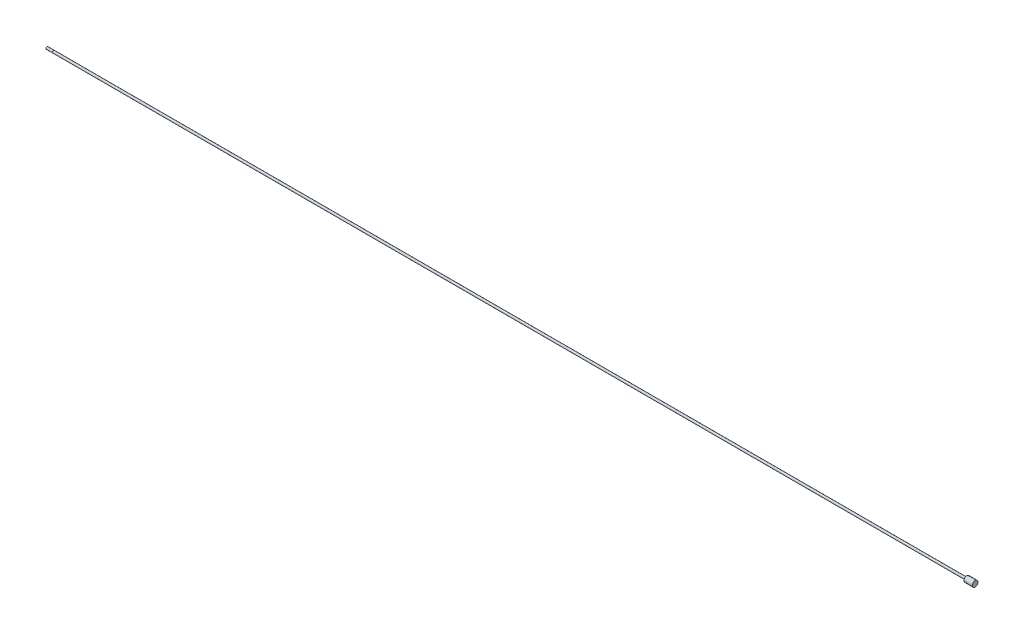
SolidWorks part; units mm, degrees
ref_plane "Front Plane" through (0, 0, 0) normal (0, 0, 1) x (1, 0, 0)
ref_plane "Top Plane" through (0, 0, 0) normal (0, 1, 0) x (1, 0, 0)
ref_plane "Right Plane" through (0, 0, 0) normal (1, 0, 0) x (0, 0, -1)
sketch "Sketch1" plane through (0, 0, 0) normal (0, 0, 1) x (1, 0, 0)
  line L0 (0, 0) -> (0, 1.5875)
  line L1 (0, 1.5875) -> (1291.463, 1.5875)
  line L2 (1291.463, 1.5875) -> (1291.463, 4.0323)
  line L3 (1291.463, 4.0323) -> (1303.3248, 4.0323)
  line L4 (1303.3248, 4.0323) -> (1303.3248, 0)
  line L5 (1303.3248, 0) -> (0, 0)
  line L6 (1303.3248, 0) -> (0, 0) construction
revolve "Revolve1" add sketch "Sketch1" angle 360 about L6 reverse direction yes
cosmetic thread "Cosmetic Thread1" parameters "D1"=9.652, "D2"=2.4181
sketch "Sketch2" plane through (0, 0, 0) normal (0, 0, 1) x (1, 0, 0)
  line L0 (-9.652, 0) -> (-9.652, 1.209)
  line L1 (-9.652, 1.209) -> (-9.2735, 1.5875)
  line L2 (-9.2735, 1.5875) -> (0, 1.5875)
  line L3 (0, 1.5875) -> (0, 0)
  line L4 (0, 0) -> (-9.652, 0)
  line L5 (0, 0) -> (-9.652, 0) construction
revolve "Revolve2" add sketch "Sketch2" angle 360 about L5 reverse direction yes
ref_plane "Plane1" through (0, 0, 0) normal (1, 0, 0) x (0, 0, -1)
ref_plane "Plane2" through (0, 0, 0) normal (1, 0, 0) x (0, 0, -1)
ref_plane "Plane3" through (2594.7878, 0, 0) normal (1, 0, 0) x (0, 0, -1)
ref_plane "Plane4" through (-9.652, 0, 0) normal (1, 0, 0) x (0, 0, -1)
sketch "Sketch3" plane through (0, 0, 0) normal (0, 0, 1) x (1, 0, 0)
  line L0 (-0.254, 1.8415) -> (-0.254, 1.3335)
  line L1 (-0.254, 1.3335) -> (0, 1.3335)
  line L2 (0, 1.3335) -> (0, 1.8415)
  line L3 (0, 1.8415) -> (-0.254, 1.8415)
  line L4 (0, 0) -> (-0.254, 0) construction
revolve "Cut-Revolve1" cut sketch "Sketch3" angle 360 about L4 reverse direction yes
ref_plane "Plane5" through (0, 0, 0) normal (1, 0, 0) x (0, 0, -1)
ref_plane "Plane6" through (0, 0, 0) normal (1, 0, 0) x (0, 0, -1)
ref_plane "Plane7" through (-9.652, 0, 0) normal (1, 0, 0) x (0, 0, -1)
ref_plane "dia1 XY" through (0, 0, 0) normal (1, 0, 0) x (0, 0, -1)
ref_plane "dia1 XZ" through (0, 1.5875, 0) normal (0, -1, 0) x (-1, 0, 0)
ref_plane "dia1 YZ" through (0, 0, 0) normal (0, 0, -1) x (-1, 0, 0)
ref_axis "dia1 X" through (0, 1.5875, 80.9) along (0, 0, -1)
ref_axis "dia1 Y" through (0, -50, 0) along (0, 1, 0)
ref_axis "dia1 Z" through (80.9, 1.5875, 0) along (-1, 0, 0)
sketch3d "dia1"
  point P0 (0, 1.5875, 0)
ref_plane "dia12 XY" through (0, 0, 0) normal (1, 0, 0) x (0, 0, -1)
ref_plane "dia12 XZ" through (0, 0, 0) normal (0, -1, 0) x (-1, 0, 0)
ref_plane "dia12 YZ" through (0, 0, 7.6835) normal (0, 0, -1) x (-1, 0, 0)
ref_axis "dia12 X" through (0, 0, 80.9) along (0, 0, -1)
ref_axis "dia12 Y" through (0, -50, 7.6835) along (0, 1, 0)
ref_axis "dia12 Z" through (80.9, 0, 7.6835) along (-1, 0, 0)
sketch3d "dia12"
  point P0 (0, 0, 7.6835)
ref_plane "dia1r XY" through (0, 0, 0) normal (1, 0, 0) x (0, 0, -1)
ref_plane "dia1r XZ" through (0, 0, 0) normal (0, -1, 0) x (-1, 0, 0)
ref_plane "dia1r YZ" through (0, 0, 4.5593) normal (0, 0, -1) x (-1, 0, 0)
ref_axis "dia1r X" through (0, 0, 80.9) along (0, 0, -1)
ref_axis "dia1r Y" through (0, -50, 4.5593) along (0, 1, 0)
ref_axis "dia1r Z" through (80.9, 0, 4.5593) along (-1, 0, 0)
sketch3d "dia1r"
  point P0 (0, 0, 4.5593)
ref_plane "dia2 XY" through (0, 0, 0) normal (1, 0, 0) x (0, 0, -1)
ref_plane "dia2 XZ" through (0, -1.5875, 0) normal (0, -1, 0) x (-1, 0, 0)
ref_plane "dia2 YZ" through (0, 0, 0) normal (0, 0, -1) x (-1, 0, 0)
ref_axis "dia2 X" through (0, -1.5875, 80.9) along (0, 0, -1)
ref_axis "dia2 Y" through (0, -50, 0) along (0, 1, 0)
ref_axis "dia2 Z" through (80.9, -1.5875, 0) along (-1, 0, 0)
sketch3d "dia2"
  point P0 (0, -1.5875, 0)
ref_plane "dia22 XY" through (0, 0, 0) normal (1, 0, 0) x (0, 0, -1)
ref_plane "dia22 XZ" through (0, 0, 0) normal (0, -1, 0) x (-1, 0, 0)
ref_plane "dia22 YZ" through (0, 0, -7.6835) normal (0, 0, -1) x (-1, 0, 0)
ref_axis "dia22 X" through (0, 0, 80.9) along (0, 0, -1)
ref_axis "dia22 Y" through (0, -50, -7.6835) along (0, 1, 0)
ref_axis "dia22 Z" through (80.9, 0, -7.6835) along (-1, 0, 0)
sketch3d "dia22"
  point P0 (0, 0, -7.6835)
ref_plane "dia2r XY" through (0, 0, 0) normal (1, 0, 0) x (0, 0, -1)
ref_plane "dia2r XZ" through (0, 0, 0) normal (0, -1, 0) x (-1, 0, 0)
ref_plane "dia2r YZ" through (0, 0, -4.5593) normal (0, 0, -1) x (-1, 0, 0)
ref_axis "dia2r X" through (0, 0, 80.9) along (0, 0, -1)
ref_axis "dia2r Y" through (0, -50, -4.5593) along (0, 1, 0)
ref_axis "dia2r Z" through (80.9, 0, -4.5593) along (-1, 0, 0)
sketch3d "dia2r"
  point P0 (0, 0, -4.5593)
ref_plane "rl1 XY" through (-9.652, 0, 0) normal (1, 0, 0) x (0, 0, -1)
ref_plane "rl1 XZ" through (0, 0, 0) normal (0, -1, 0) x (-1, 0, 0)
ref_plane "rl1 YZ" through (0, 0, 0) normal (0, 0, -1) x (-1, 0, 0)
ref_axis "rl1 X" through (-9.652, 0, 80.9) along (0, 0, -1)
ref_axis "rl1 Y" through (-9.652, -50, 0) along (0, 1, 0)
ref_axis "rl1 Z" through (80.9, 0, 0) along (-1, 0, 0)
sketch3d "rl1"
  point P0 (-9.652, 0, 0)
ref_plane "rl2 XY" through (0, 0, 0) normal (1, 0, 0) x (0, 0, -1)
ref_plane "rl2 XZ" through (0, 0, 0) normal (0, -1, 0) x (-1, 0, 0)
ref_plane "rl2 YZ" through (0, 0, 0) normal (0, 0, -1) x (-1, 0, 0)
ref_axis "rl2 X" through (0, 0, 80.9) along (0, 0, -1)
ref_axis "rl2 Y" through (0, -50, 0) along (0, 1, 0)
ref_axis "rl2 Z" through (80.9, 0, 0) along (-1, 0, 0)
sketch3d "rl2"
  point P0 (0, 0, 0)
ref_plane "rod_cp XY" through (0, 0, 0) normal (1, 0, 0) x (0, 0, -1)
ref_plane "rod_cp XZ" through (0, 0, 0) normal (0, -1, 0) x (-1, 0, 0)
ref_plane "rod_cp YZ" through (0, 0, 0) normal (0, 0, -1) x (-1, 0, 0)
ref_axis "rod_cp X" through (0, 0, 80.9) along (0, 0, -1)
ref_axis "rod_cp Y" through (0, -50, 0) along (0, 1, 0)
ref_axis "rod_cp Z" through (80.9, 0, 0) along (-1, 0, 0)
sketch3d "rod_cp"
  point P0 (0, 0, 0)
ref_plane "thd1 XY" through (-9.652, 0, 0) normal (1, 0, 0) x (0, 0, -1)
ref_plane "thd1 XZ" through (0, 1.5875, 0) normal (0, -1, 0) x (-1, 0, 0)
ref_plane "thd1 YZ" through (0, 0, 0) normal (0, 0, -1) x (-1, 0, 0)
ref_axis "thd1 X" through (-9.652, 1.5875, 80.9) along (0, 0, -1)
ref_axis "thd1 Y" through (-9.652, -50, 0) along (0, 1, 0)
ref_axis "thd1 Z" through (80.9, 1.5875, 0) along (-1, 0, 0)
sketch3d "thd1"
  point P0 (-9.652, 1.5875, 0)
ref_plane "thd2 XY" through (-9.652, 0, 0) normal (1, 0, 0) x (0, 0, -1)
ref_plane "thd2 XZ" through (0, -1.5875, 0) normal (0, -1, 0) x (-1, 0, 0)
ref_plane "thd2 YZ" through (0, 0, 0) normal (0, 0, -1) x (-1, 0, 0)
ref_axis "thd2 X" through (-9.652, -1.5875, 80.9) along (0, 0, -1)
ref_axis "thd2 Y" through (-9.652, -50, 0) along (0, 1, 0)
ref_axis "thd2 Z" through (80.9, -1.5875, 0) along (-1, 0, 0)
sketch3d "thd2"
  point P0 (-9.652, -1.5875, 0)
ref_plane "to_rod_clevis XY" through (-9.652, 0, 0) normal (1, 0, 0) x (0, 0, -1)
ref_plane "to_rod_clevis XZ" through (0, 0, 0) normal (0, -1, 0) x (-1, 0, 0)
ref_plane "to_rod_clevis YZ" through (0, 0, 0) normal (0, 0, -1) x (-1, 0, 0)
ref_axis "to_rod_clevis X" through (-9.652, 0, 80.9) along (0, 0, -1)
ref_axis "to_rod_clevis Y" through (-9.652, -50, 0) along (0, 1, 0)
ref_axis "to_rod_clevis Z" through (80.9, 0, 0) along (-1, 0, 0)
sketch3d "to_rod_clevis"
  point P0 (-9.652, 0, 0)
